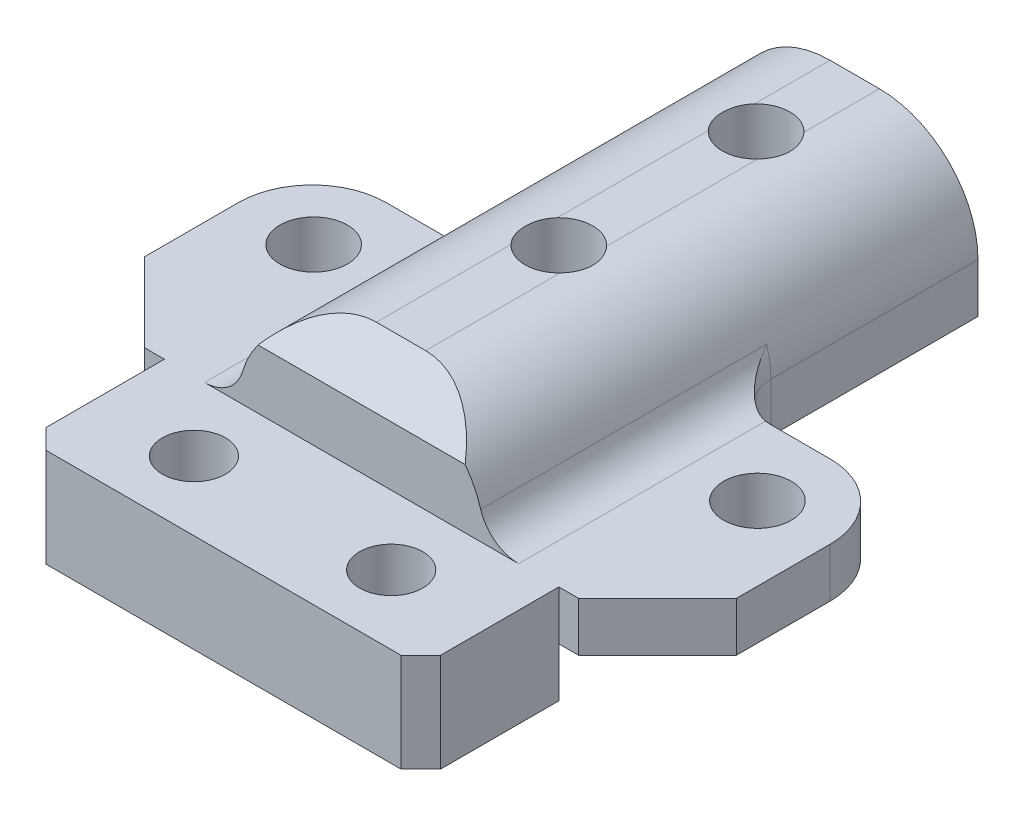
SolidWorks part; units mm, degrees
ref_plane "Front Plane" through (0, 0, 0) normal (0, 0, 1) x (1, 0, 0)
ref_plane "Top Plane" through (0, 0, 0) normal (0, 1, 0) x (1, 0, 0)
ref_plane "Right Plane" through (0, 0, 0) normal (1, 0, 0) x (0, 0, -1)
sketch "Sketch1" plane through (0, 0, 0) normal (0, 1, 0) x (1, 0, 0)
  line L0 (0, 3.5) -> (0, 20.5328) construction
  line L1 (-10, 3.5) -> (10, 3.5)
  line L2 (-10, 3.5) -> (-10, -3.5)
  line L3 (-10, -3.5) -> (10, -3.5)
  line L4 (10, 3.5) -> (10, -3.5)
  line L5 (-10, 3.5) -> (10, -3.5) construction
  line L6 (-10, -3.5) -> (10, 3.5) construction
  line L8 (-15, 3.5) -> (15, 3.5)
  line L9 (-15, 3.5) -> (-15, 28.5)
  line L10 (-15, 28.5) -> (15, 28.5)
  line L11 (15, 3.5) -> (15, 28.5)
  line L12 (-15, 3.5) -> (15, 28.5) construction
  line L13 (-15, 28.5) -> (15, 3.5) construction
  point P0 (0, 0)
  point P8 (0, 16)
  dimension "D1" = 20
  dimension "D2" = 7
  dimension "D3" = 25
  dimension "D4" = 30
extrude "Boss-Extrude1" add sketch "Sketch1" along normal blind 5 contours L4 L1 L2 L3 | L8 L11 L10 L9 L1 region at (0, 0, -16) region at (0, 0, 0)
sketch "Sketch6" plane through (0, 0, 0) normal (0, -1, 0) x (1, 0, 0)
  line L0 (0, 0) -> (0, 4.3134) construction
  circle A0 centre (-5, 0) radius 1.6
  circle A1 centre (5, 0) radius 1.6
  dimension "D1" = 3.2
  dimension "D2" = 10
extrude "Cut-Extrude4" cut sketch "Sketch6" against normal through all
sketch "Sketch8" plane through (0, 0, -28.5) normal (0, 0, -1) x (-1, 0, 0)
  line L0 (15, 5) -> (15, 0) construction
  line L1 (-15, 0) -> (15, 0)
  line L2 (-15, 0) -> (-15, 2.5)
  line L3 (-15, 2.5) -> (15, 2.5)
  line L4 (15, 0) -> (15, 2.5)
  dimension "D1" = 2.5
extrude "Cut-Extrude6" cut sketch "Sketch8" against normal blind 25
sketch "Sketch9" plane through (0, 5, 0) normal (0, 1, 0) x (1, 0, 0)
  line L1 (-6.25, 28.5) -> (6.25, 28.5)
  line L2 (-6.25, 28.5) -> (-6.25, 3.5)
  line L3 (-6.25, 3.5) -> (6.25, 3.5)
  line L4 (6.25, 28.5) -> (6.25, 3.5)
  line L5 (-15, 28.5) -> (15, 28.5) construction
  line L6 (0, 0) -> (0, 8.0564) construction
  line L7 (10, 3.5) -> (15, 3.5) construction
  dimension "D2" = 12.5
extrude "Boss-Extrude4" add sketch "Sketch9" along normal blind 5
sketch "Sketch10" plane through (0, 0, -28.5) normal (0, 0, -1) x (-1, 0, 0)
  line L0 (10, 2.5) -> (-10, 2.5) construction
  circle A0 centre (0, 2.5) radius 3.95
  dimension "D1" = 7.9
extrude "Cut-Extrude7" cut sketch "Sketch10" against normal blind 20
chamfer "Chamfer7" distance 4 angle 45 2 edges at (-15, 3.75, -3.5) (15, 3.75, -3.5)
chamfer "Chamfer11" distance 1 angle 45 2 edges at (-10, 2.5, 3.5) (10, 2.5, 3.5)
chamfer "Chamfer14" distance 2 angle 45 1 edges at (0, 10, -3.5) tangent propagation no
sketch "Sketch15" plane through (0, 5, 0) normal (0, 1, 0) x (1, 0, 0)
  line L0 (-6.25, 28.5) -> (-6.25, 5.5) construction
  line L1 (-15, 28.5) -> (-6.25, 28.5)
  line L2 (-15, 28.5) -> (-15, 16)
  line L3 (-15, 16) -> (-6.25, 16)
  line L4 (-6.25, 28.5) -> (-6.25, 16)
  line L5 (6.25, 5.5) -> (6.25, 28.5) construction
  line L6 (15, 28.5) -> (6.25, 28.5)
  line L7 (15, 28.5) -> (15, 16)
  line L8 (15, 16) -> (6.25, 16)
  line L9 (6.25, 28.5) -> (6.25, 16)
  dimension "D1" = 12.5
extrude "Cut-Extrude10" cut sketch "Sketch15" against normal through all
sketch "Sketch16" plane through (0, 5, 0) normal (0, 1, 0) x (1, 0, 0)
  line L0 (0, 0) -> (0, 8.7782) construction
  circle A0 centre (-11.25, 12.3177) radius 1.7145
  circle A1 centre (11.25, 12.3177) radius 1.7145
  dimension "D3" = 3.429
  dimension "D1" = 3.75
  dimension "D2" = 3.6823
extrude "Cut-Extrude11" cut sketch "Sketch16" against normal through all
fillet "Fillet1" radius 3.75 2 edges at (-15, 3.75, -16) (15, 3.75, -16)
fillet "Fillet2" radius 5 2 edges at (6.25, 10, -17) (-6.25, 10, -17)
fillet "Fillet3" radius 2 2 edges at (-6.25, 5, -9.75) (6.25, 5, -9.75)
fillet "Fillet4" radius 2 4 edges at (-6.1976, 5.7218, -16) (6.1976, 5.7218, -16) (-6.25, 3.75, -16) (6.25, 3.75, -16)
sketch "Sketch17" plane through (0, 10, 0) normal (0, 1, 0) x (1, 0, 0)
  line L0 (1.25, 28.5) -> (-1.25, 28.5) construction
  circle A0 centre (0, 23.5) radius 1.7145
  circle A1 centre (0, 13.5) radius 1.7145
  dimension "D1" = 3.429
  dimension "D2" = 10
  dimension "D3" = 5
extrude "Cut-Extrude12" cut sketch "Sketch17" against normal through all
